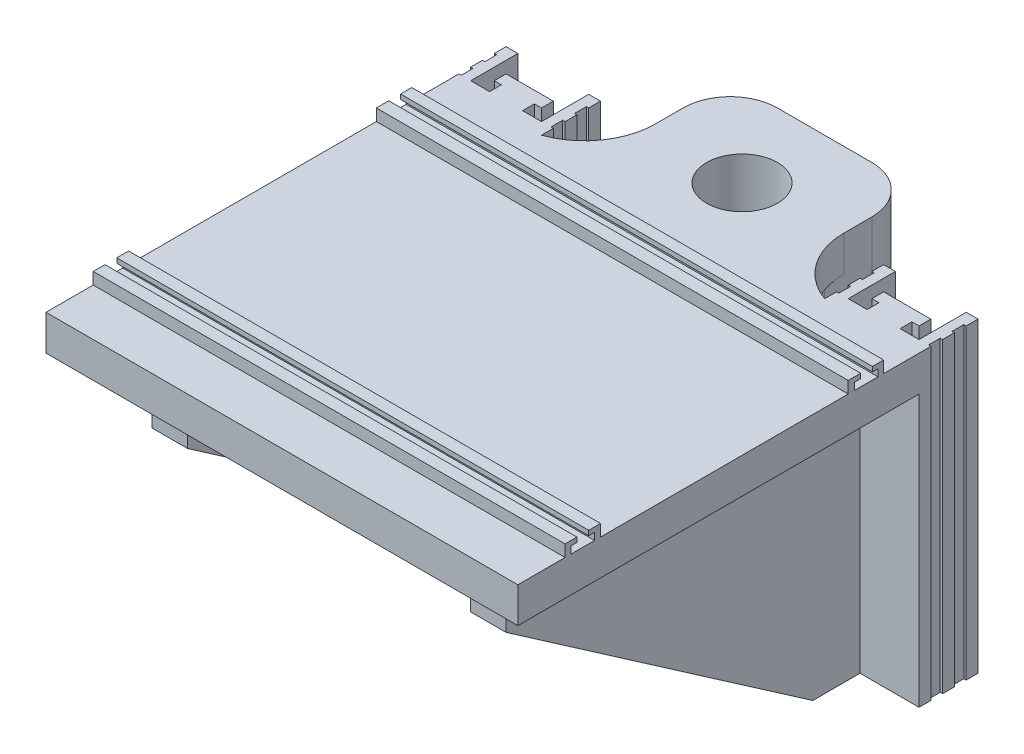
SolidWorks part; units mm, degrees
ref_plane "前视基准面" through (0, 0, 0) normal (0, 0, 1) x (1, 0, 0)
ref_plane "上视基准面" through (0, 0, 0) normal (0, 1, 0) x (1, 0, 0)
ref_plane "右视基准面" through (0, 0, 0) normal (1, 0, 0) x (0, 0, -1)
sketch "草图1" plane through (0, 0, 0) normal (0, 1, 0) x (1, 0, 0)
  line L0 (0, 0) -> (-60, 0) construction
  line L1 (0, 0) -> (60, 0) construction
  line L2 (-60, 0) -> (-60, 20)
  line L3 (-60, 20) -> (-65, 20)
  line L4 (-65, 20) -> (-65, 0)
  line L5 (-65, 0) -> (-73, 0)
  line L18 (-60, -5) -> (-60, 0)
  line L19 (0, 0) -> (0, 39.2368) construction
  line L37 (-73, 0) -> (-73, 5)
  line L38 (-73, 5) -> (-70, 5)
  line L49 (-70, 5) -> (-70, 10)
  line L50 (-70, 10) -> (-90, 10)
  line L51 (-90, 10) -> (-90, 5)
  line L52 (-90, 5) -> (-87, 5)
  line L53 (-87, 5) -> (-87, 0)
  line L54 (-87, 0) -> (-95, 0)
  line L59 (-95, 0) -> (-95, 20)
  line L60 (-95, 20) -> (-100, 20)
  line L61 (-100, 20) -> (-100, -5)
  line L62 (-100, -5) -> (-60, -5)
  line L63 (73, 0) -> (73, 5)
  line L64 (87, 5) -> (87, 0)
  line L65 (90, 5) -> (87, 5)
  line L66 (73, 5) -> (70, 5)
  line L67 (70, 5) -> (70, 10)
  line L68 (70, 10) -> (90, 10)
  line L69 (90, 10) -> (90, 5)
  line L70 (95, 0) -> (95, 20)
  line L71 (95, 20) -> (100, 20)
  line L72 (87, 0) -> (95, 0)
  line L73 (100, 20) -> (100, -5)
  line L74 (100, -5) -> (60, -5)
  line L75 (60, -5) -> (60, 0)
  line L76 (60, 0) -> (60, 20)
  line L77 (65, 20) -> (65, 0)
  line L78 (65, 0) -> (73, 0)
  line L79 (60, 20) -> (65, 20)
extrude "凸台-拉伸1" add sketch "草图1" along normal blind 130
sketch "草图3" plane through (0, 130, 0) normal (0, 1, 0) x (1, 0, 0)
  line L0 (-100, 15) -> (-100, 10)
  line L1 (-100, 20) -> (-100, -5) construction
  line L2 (-100, 15) -> (-99, 15)
  line L3 (-99, 15) -> (-99, 10)
  line L4 (-99, 10) -> (-100, 10)
  line L5 (-100, 5) -> (-100, 0)
  line L6 (-100, 5) -> (-99, 5)
  line L7 (-99, 5) -> (-99, 0)
  line L8 (-99, 0) -> (-100, 0)
  line L9 (-60, 15) -> (-61, 15)
  line L10 (-60, -5) -> (-60, 20) construction
  line L11 (-61, 15) -> (-61, 10)
  line L12 (-61, 10) -> (-60, 10)
  line L13 (0, 0) -> (0, 19.875) construction
  line L14 (-60, 5) -> (-61, 5)
  line L15 (-61, 5) -> (-61, 0)
  line L16 (-61, 0) -> (-60, 0)
  line L17 (-60, 0) -> (-60, 5)
  line L18 (-60, 15) -> (-60, 10)
  line L19 (61, 0) -> (60, 0)
  line L20 (60, 0) -> (60, 5)
  line L21 (61, 5) -> (61, 0)
  line L22 (60, 5) -> (61, 5)
  line L23 (61, 10) -> (60, 10)
  line L24 (60, 15) -> (60, 10)
  line L25 (61, 15) -> (61, 10)
  line L26 (60, 15) -> (61, 15)
  line L27 (99, 0) -> (100, 0)
  line L28 (99, 5) -> (99, 0)
  line L29 (100, 5) -> (100, 0)
  line L30 (100, 5) -> (99, 5)
  line L31 (99, 10) -> (100, 10)
  line L32 (99, 15) -> (99, 10)
  line L33 (100, 15) -> (100, 10)
  line L34 (100, 15) -> (99, 15)
extrude "切除-拉伸3" cut sketch "草图3" against normal through all
sketch "草图5" plane through (0, 0, 5) normal (0, 0, 1) x (1, 0, 0)
  line L0 (-100, 130) -> (100, 130)
  line L9 (-100, 130) -> (-100, 115)
  line L10 (-100, 130) -> (-100, 0) construction
  line L11 (-100, 115) -> (100, 115)
  line L12 (100, 130) -> (100, 0) construction
  line L13 (100, 115) -> (100, 130)
extrude "凸台-拉伸2" add sketch "草图5" along normal blind 170
sketch "草图6" plane through (0, 0, 5) normal (0, 0, 1) x (1, 0, 0)
  line L0 (-60, 115) -> (-75, 115)
  line L1 (-100, 115) -> (-60, 115) construction
  line L2 (-75, 115) -> (-75, 0)
  line L3 (-100, 0) -> (-60, 0) construction
  line L4 (-75, 0) -> (-60, 0)
  line L5 (-60, 0) -> (-60, 115)
  line L6 (60, 115) -> (75, 115)
  line L7 (60, 115) -> (100, 115) construction
  line L8 (75, 115) -> (75, 0)
  line L9 (60, 0) -> (100, 0) construction
  line L10 (75, 0) -> (60, 0)
  line L11 (60, 0) -> (60, 115)
extrude "凸台-拉伸3" add sketch "草图6" along normal blind 150
sketch "草图7" plane through (-75, 0, 0) normal (-1, 0, 0) x (0, 0, 1)
  line L1 (155, 0) -> (5, 0) construction
  line L3 (155, 115) -> (155, 0) construction
  line L4 (25, 0) -> (155, 90)
  line L5 (25, 0) -> (155, 0)
  line L6 (155, 0) -> (155, 90)
extrude "切除-拉伸4" cut sketch "草图7" against normal through all
sketch "草图8" plane through (0, 130, 0) normal (0, 1, 0) x (1, 0, 0)
  line L0 (-60, -5) -> (-40, -5) construction
  line L1 (60, -5) -> (-60, -5) construction
  line L2 (-40, -5) -> (40, -5)
  line L4 (-40, -5) -> (-40, 55)
  line L5 (-40, 55) -> (40, 55)
  line L6 (40, 55) -> (40, -5)
  circle A0 centre (0, 20) radius 15
  dimension "D1" = 25
extrude "凸台-拉伸4" add sketch "草图8" against normal blind 30
fillet "圆角1" radius 30 2 edges at (40, 122.5, 5) (-40, 122.5, 5)
fillet "圆角3" radius 20 4 edges at (-40, 107.5, 5) (40, 107.5, 5) (-40, 115, -55) (40, 115, -55)
sketch "草图9" plane through (0, 130, 0) normal (0, 1, 0) x (1, 0, 0)
  line L1 (100, -175) -> (100, 0) construction
  line L2 (100, -155) -> (100, -140)
  line L3 (100, -140) -> (-100, -140)
  line L4 (-100, 0) -> (-100, -175) construction
  line L5 (-100, -140) -> (-100, -155)
  line L6 (-100, -155) -> (100, -155)
  line L8 (100, -20) -> (-100, -20)
  line L9 (-100, -20) -> (-100, -35)
  line L10 (-100, -35) -> (100, -35)
  line L11 (100, -35) -> (100, -20)
extrude "凸台-拉伸5" add sketch "草图9" along normal blind 5
sketch "草图10" plane through (0, 135, 0) normal (0, 1, 0) x (1, 0, 0)
  line L1 (-100, -24.742) -> (100, -24.742)
  line L2 (-100, -140) -> (-100, -155) construction
  line L3 (-100, -150) -> (-100, -145)
  line L4 (-100, -145) -> (100, -145)
  line L5 (100, -155) -> (100, -140) construction
  line L6 (100, -145) -> (100, -150)
  line L7 (100, -150) -> (-100, -150)
  line L8 (-100, -20) -> (-100, -35) construction
  line L9 (100, -35) -> (100, -20) construction
  line L10 (100, -24.742) -> (100, -29.742)
  line L11 (100, -29.742) -> (-100, -29.742)
  line L12 (-100, -29.742) -> (-100, -24.742)
extrude "切除-拉伸5" cut sketch "草图10" against normal blind 2
sketch "草图11" plane through (0, 133, 0) normal (0, 1, 0) x (1, 0, 0)
  line L0 (-100, -22.371) -> (100, -22.371)
  line L1 (-100, -150) -> (-100, -155) construction
  line L2 (-100, -152.5) -> (-100, -142.5)
  line L3 (-100, -140) -> (-100, -145) construction
  line L4 (-100, -142.5) -> (100, -142.5)
  line L5 (100, -145) -> (100, -140) construction
  line L6 (100, -142.5) -> (100, -152.5)
  line L7 (100, -155) -> (100, -150) construction
  line L8 (100, -152.5) -> (-100, -152.5)
  line L9 (-100, -20) -> (-100, -24.742) construction
  line L10 (100, -24.742) -> (100, -20) construction
  line L11 (100, -22.371) -> (100, -32.371)
  line L12 (100, -35) -> (100, -29.742) construction
  line L13 (100, -32.371) -> (-100, -32.371)
  line L14 (-100, -29.742) -> (-100, -35) construction
  line L15 (-100, -32.371) -> (-100, -22.371)
extrude "切除-拉伸6" cut sketch "草图11" against normal blind 3
